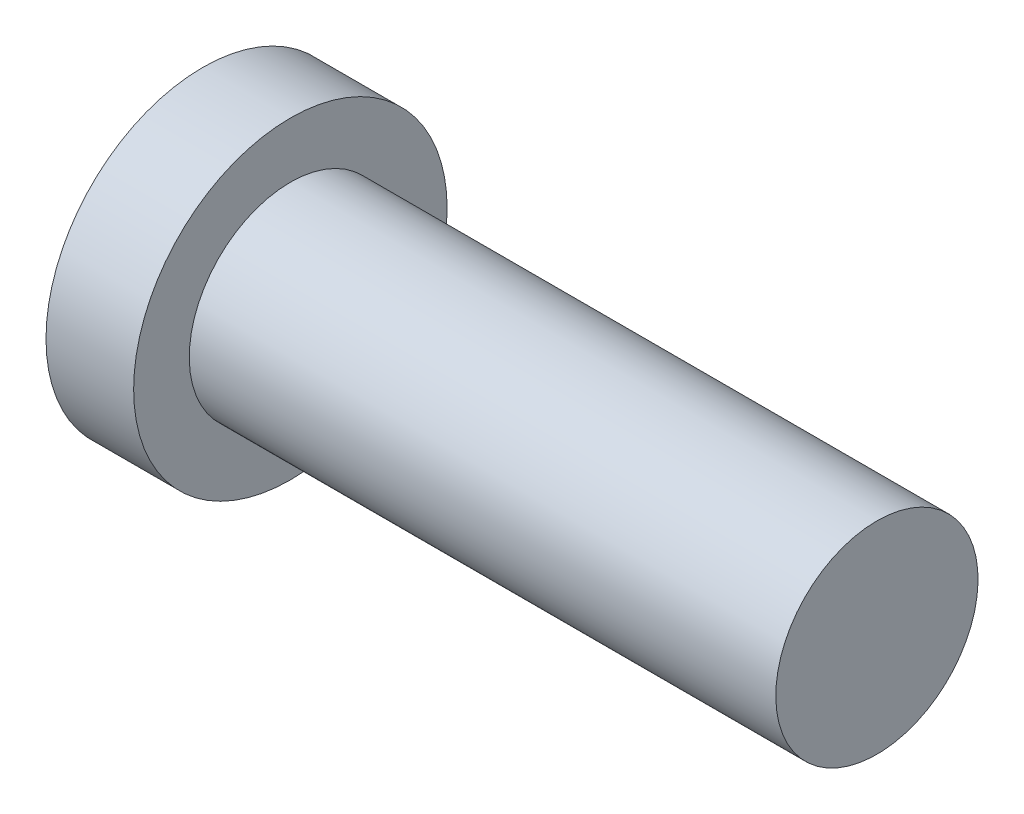
SolidWorks part; units mm, degrees
ref_plane "Front" through (0, 0, 0) normal (0, 0, 1) x (1, 0, 0)
ref_plane "Top" through (0, 0, 0) normal (0, 1, 0) x (1, 0, 0)
ref_plane "Right" through (0, 0, 0) normal (1, 0, 0) x (0, 0, -1)
sketch "Sketch1" plane through (-21.0632, 25.6102, 0) normal (0, 0, 1) x (0, -1, 0)
  line L0 (25.6102, 21.0632) -> (26.0002, 21.0632)
  line L1 (26.0002, 21.0632) -> (26.0002, 21.3546)
  line L2 (26.2375, 21.6181) -> (27.9352, 21.7966)
  line L3 (27.9352, 21.7966) -> (27.9352, 23.0966)
  line L4 (27.9352, 23.0966) -> (27.1102, 23.0966)
  line L5 (27.1102, 23.0966) -> (27.1102, 31.7966)
  line L6 (27.1102, 31.7966) -> (25.6102, 31.7966)
  line L7 (25.6102, 31.7966) -> (25.6102, 21.0632)
  line L8 (25.6102, 50.0506) -> (25.6102, -3.3772) construction
  line L9 (26.0002, 21.5932) -> (30.1572, 21.5932) construction
  arc A0 (26.0002, 21.3546) -> (26.2375, 21.6181) centre (26.2652, 21.3546) cw
  dimension "D7" = 6
revolve "Revolve1" add sketch "Sketch1" angle 360 about L8
equation "\"D3@Sketch1\" = \"l2@Sketch1\" / 2"
